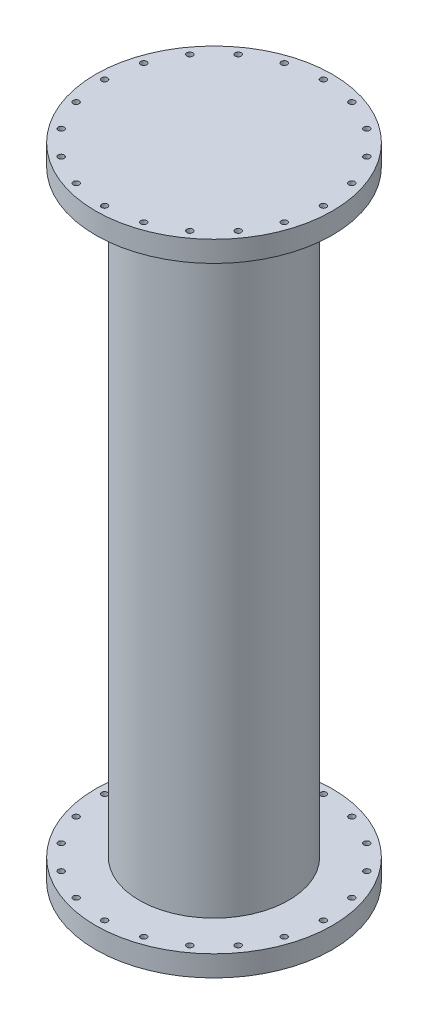
SolidWorks part; units mm, degrees
ref_plane "Plan de face" through (0, 0, 0) normal (0, 0, 1) x (1, 0, 0)
ref_plane "Plan de dessus" through (0, 0, 0) normal (0, 1, 0) x (1, 0, 0)
ref_plane "Plan de droite" through (0, 0, 0) normal (1, 0, 0) x (0, 0, -1)
sketch "Esquisse1" plane through (0, 0, 0) normal (0, 0, 1) x (1, 0, 0)
  line L0 (0, 0) -> (0, -1756.5308) construction
  line L1 (0, 0) -> (396, 0)
  line L2 (0, 0) -> (0, -70)
  line L3 (0, -70) -> (200, -70)
  line L4 (396, 0) -> (396, -70)
  line L26 (250, -70) -> (396, -70)
  line L27 (250, -2070) -> (396, -2070)
  line L29 (200, -70) -> (200, -2070)
  line L31 (250, -70) -> (250, -2070)
  line L32 (0, -2070) -> (200, -2070)
  line L33 (0, -2070) -> (0, -2140)
  line L34 (0, -2140) -> (396, -2140)
  line L35 (396, -2070) -> (396, -2140)
  dimension "D1" = 396
  dimension "D2" = 70
  dimension "D3" = 70
  dimension "D4" = 396
  dimension "D5" = 250
  dimension "D6" = 200
  dimension "D7" = 2000
revolve "Révolution1" add sketch "Esquisse1" angle 360 about L0
sketch "Esquisse2" plane through (0, 0, 0) normal (0, 1, 0) x (1, 0, 0)
  circle A0 centre (366, 0) radius 10
  dimension "D2" = 20
  dimension "D1" = 366
extrude "Enlèv. mat.-Extru.1" cut sketch "Esquisse2" against normal through all
pattern_circular "Répétition circulaire1" count 20 over 360 about axis through (0, 0, 0) along (0, 1, 0) of "Enlèv. mat.-Extru.1"
sketch "Esquisse3" plane through (0, -2140, 0) normal (0, 1, 0) x (1, 0, 0)
  circle A0 centre (0, 0) radius 255.3935
